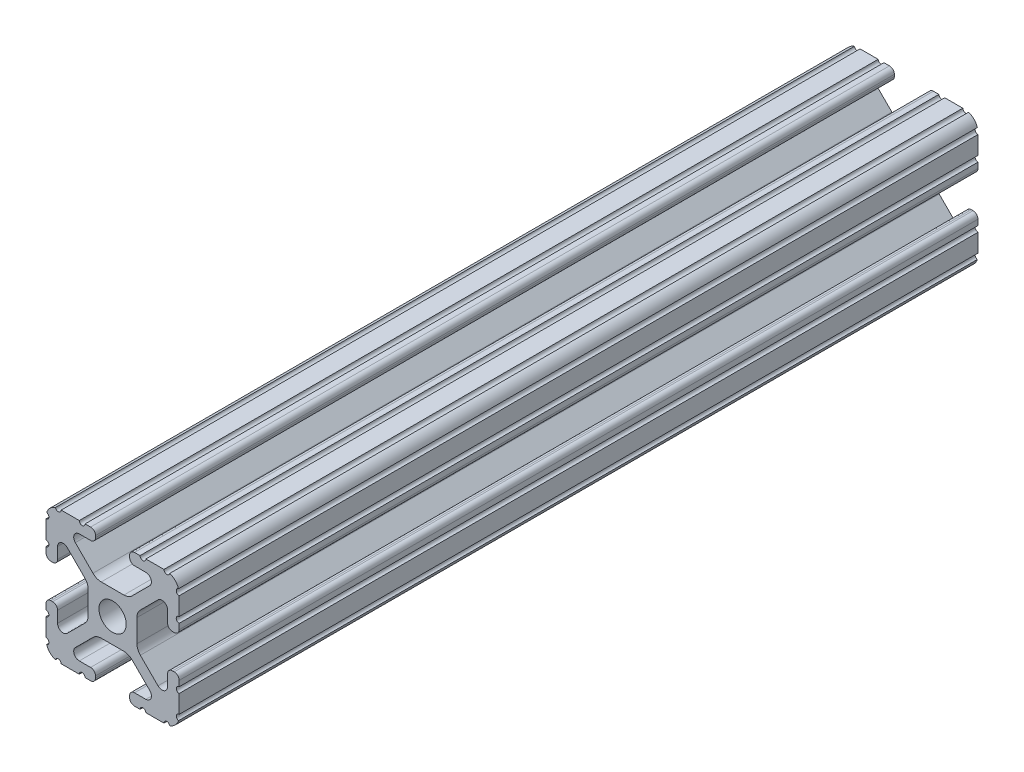
SolidWorks part; units mm, degrees
ref_plane "Front Plane" through (0, 0, 0) normal (0, 0, 1) x (1, 0, 0)
ref_plane "Top Plane" through (0, 0, 0) normal (0, 1, 0) x (1, 0, 0)
ref_plane "Right Plane" through (0, 0, 0) normal (1, 0, 0) x (0, 0, -1)
sketch "Sketch2" plane through (0, 0, 0) normal (0, 0, 1) x (1, 0, 0)
  line L0 (0, 12.7) -> (0, -12.7) construction
  line L1 (-12.7, 0) -> (12.7, 0) construction
  line L2 (3.2512, -12.7) -> (12.7, -12.7)
  line L3 (12.7, -12.7) -> (12.7, -3.2512)
  line L4 (3.2512, -12.7) -> (3.2512, -10.4902)
  line L5 (3.2512, -10.4902) -> (8.9276, -10.4902)
  line L6 (8.9276, -10.4902) -> (3.0856, -4.6482)
  line L7 (0, 0) -> (12.7, -12.7) construction
  line L8 (12.7, -3.2512) -> (10.4902, -3.2512)
  line L9 (10.4902, -3.2512) -> (10.4902, -8.9276)
  line L10 (10.4902, -8.9276) -> (4.6482, -3.0856)
  circle A0 centre (0, 0) radius 2.6035
  arc A1 (6.3485, -10.4902) -> (7.1039, -8.6665) centre (6.3485, -9.4219) ccw construction
  point P8 (0, -4.6482)
  dimension "Center Hole Diameter" = 5.207
  dimension "Rail Height" = 25.4
  dimension "Rail Width" = 25.4
  dimension "T-Slot Width" = 6.5024
  dimension "Slot Inner Width" = 14.8336
  dimension "Thickness" = 2.2098
  dimension "Slot Depth" = 5.842
  dimension "D1" = 2.2098
sketch "Sketch3" plane through (0, 0, 0) normal (1, 0, 0) x (0, 0, -1)
  line L0 (-76.2, -12.7) -> (76.2, -12.7) construction
  line L1 (-68.58, 0) -> (68.58, 0) construction
  dimension "Length" = 152.4
  dimension "D1" = 137.16
sketch "Sketch4" plane through (0, 0, 0) normal (0, 0, 1) x (1, 0, 0)
  line L0 (4.1904, -12.7) -> (10.1173, -12.7)
  line L1 (3.2512, -12.7) -> (12.7, -12.7) construction
  line L2 (3.2512, -12.7) -> (3.2512, -10.4902) construction
  line L3 (3.2512, -10.4902) -> (8.9276, -10.4902) construction
  line L4 (3.2512, -11.4294) -> (3.2512, -11.7608)
  line L5 (4.1904, -10.4902) -> (6.3485, -10.4902)
  line L6 (0, -4.6482) -> (2.164, -4.6482)
  line L7 (8.9276, -10.4902) -> (3.0856, -4.6482) construction
  line L8 (3.7373, -5.2999) -> (7.1039, -8.6665)
  line L9 (12.7, -12.7) -> (12.7, -3.2512) construction
  line L10 (10.4902, -8.9276) -> (4.6482, -3.0856) construction
  line L11 (10.4902, -3.2512) -> (10.4902, -8.9276) construction
  line L12 (10.4902, -6.3485) -> (10.4902, -4.1904)
  line L13 (12.7, -3.2512) -> (10.4902, -3.2512) construction
  line L14 (11.4294, -3.2512) -> (11.7608, -3.2512)
  line L15 (12.7, -4.1904) -> (12.7, -10.1173)
  line L16 (8.6665, -7.1039) -> (5.2999, -3.7373)
  line L17 (4.6482, 0) -> (4.6482, -2.164)
  line L18 (-12.7, 0) -> (12.7, 0) construction
  line L19 (0, -4.6482) -> (0, -2.6035)
  line L20 (0, 12.7) -> (0, -12.7) construction
  line L21 (4.6482, 0) -> (2.6035, 0)
  arc A0 (3.2512, -11.7608) -> (4.1904, -12.7) centre (4.1904, -11.7608) ccw
  arc A2 (3.2512, -11.4294) -> (4.1904, -10.4902) centre (4.1904, -11.4294) cw
  arc A3 (6.3485, -10.4902) -> (7.1039, -8.6665) centre (6.3485, -9.4219) ccw
  arc A4 (2.164, -4.6482) -> (3.7373, -5.2999) centre (2.164, -6.8732) cw
  arc A5 (10.1173, -12.7) -> (12.7, -10.1173) centre (10.1173, -10.1173) ccw
  arc A6 (8.6665, -7.1039) -> (10.4902, -6.3485) centre (9.4219, -6.3485) ccw
  arc A7 (10.4902, -4.1904) -> (11.4294, -3.2512) centre (11.4294, -4.1904) cw
  arc A8 (11.7608, -3.2512) -> (12.7, -4.1904) centre (11.7608, -4.1904) cw
  arc A9 (5.2999, -3.7373) -> (4.6482, -2.164) centre (6.8732, -2.164) cw
  circle A10 centre (0, 0) radius 2.6035 construction
  arc A11 (0, -2.6035) -> (2.6035, 0) centre (0, 0) ccw
  dimension "D1" = 2.5827
  dimension "D2" = 2.225
  dimension "D3" = 0.9392
extrude "Boss-Extrude1" add sketch "Sketch4" along normal mid plane 152.4
sketch "Sketch5" plane through (0, 0, 0) normal (0, 0, 1) x (1, 0, 0)
  line L0 (3.2512, -12.7) -> (12.7, -12.7) construction
  line L1 (4.1904, -10.4902) -> (6.3485, -10.4902) construction
  line L3 (0, 0) -> (12.7, -12.7) construction
  line L4 (6.3485, -10.4902) -> (6.3485, -12.7) construction
  line L5 (8.9276, -10.4902) -> (3.0856, -4.6482) construction
  circle A0 centre (10.3562, -12.7) radius 0.5524
  circle A1 centre (5.796, -12.7) radius 0.5524
  circle A2 centre (12.7, -10.3562) radius 0.5524
  circle A3 centre (12.7, -5.796) radius 0.5524
  point P10 (5.2694, -10.4902)
  point P12 (9.4219, -6.3485)
  dimension "D1" = 1.1049
extrude "Cut-Extrude1" cut sketch "Sketch5" against normal through all both and the other way through all
mirror "Mirror1" about plane through (0, 0, 0) normal (1, 0, 0) of bodies 137 134
mirror "Mirror2" about plane through (0, 0, 0) normal (0, 1, 0) of bodies 135
equation "\"D1@Boss-Extrude1\"=\"Length@Sketch3\""
equation "\"D1@Sketch2\"=\"Thickness@Sketch2\""
equation "\"D2@Sketch4\"=\"Slot Inner Width@Sketch2\"*0.15"
equation "\"D1@Sketch4\"=\"D3@Sketch4\"*2.75"
equation "\"D3@Sketch4\"=\"Thickness@Sketch2\"*0.425"
equation "\"D1@Sketch5\"=\"Thickness@Sketch2\"*0.5"
equation "\"D1@Sketch3\"=\"Length@Sketch3\"*0.9"
